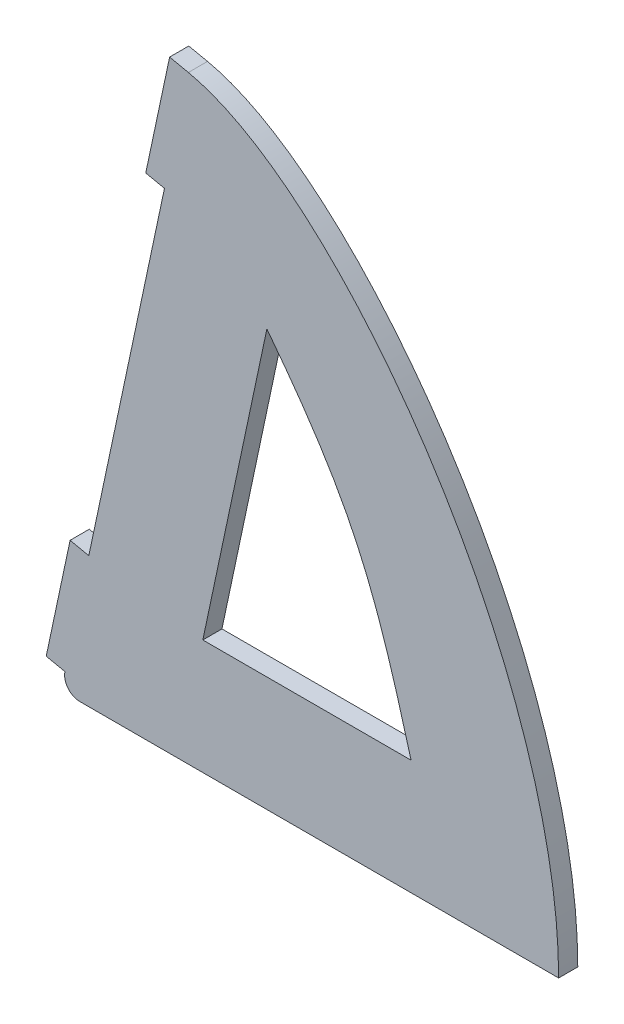
SolidWorks part; units mm, degrees
ref_plane "Front Plane" through (0, 0, 0) normal (0, 0, 1) x (1, 0, 0)
ref_plane "Top Plane" through (0, 0, 0) normal (0, 1, 0) x (1, 0, 0)
ref_plane "Right Plane" through (0, 0, 0) normal (1, 0, 0) x (0, 0, -1)
sketch "Sketch1" plane through (0, 0, 0) normal (0, 0, 1) x (1, 0, 0)
  line L0 (17.1631, 80.7461) -> (4.6129, 21.7018)
  line L1 (3.1366, 0) -> (82.55, 0)
  line L2 (-133.6738, 132.2831) -> (-145.319, 134.7583) construction
  line L3 (21.1238, 99.3798) -> (44.8991, 94.3262) construction
  line L4 (-1.4509, 104.1782) -> (-8.3265, 105.6397) construction
  line L5 (82.55, -41.9989) -> (82.55, 41.9989) construction
  line L6 (21.1238, 99.3798) -> (18.0182, 100.0399)
  line L7 (18.0182, 100.0399) -> (14.0575, 81.4062)
  line L8 (14.0575, 81.4062) -> (17.1631, 80.7461)
  line L9 (0.6521, 3.0681) -> (-2.4535, 3.7282)
  line L10 (-2.4535, 3.7282) -> (1.5072, 22.3619)
  line L11 (34.1512, 69.0431) -> (23.5248, 19.05)
  line L12 (23.5248, 19.05) -> (58.0733, 19.05)
  line L13 (1.5072, 22.3619) -> (4.6129, 21.7018)
  line L14 (0.6521, 3.0681) -> (4.6129, 21.7018) construction
  line L15 (17.1631, 80.7461) -> (21.1238, 99.3798) construction
  arc A0 (0.6521, 3.0681) -> (3.1366, 0) centre (3.1366, 2.54) ccw
  spline S0 degree 3 poles (21.1238, 99.3798) (46.7067, 93.942) (82.55, 42.6423) (82.55, 0) knots 0 0 0 0 1 1 1 1
  spline S1 degree 3 poles (34.1512, 69.0431) (48.6666, 50.286) (52.0895, 40.772) (58.0733, 19.05) knots 0 0 0 0 1 1 1 1
  point P8 (0, 0)
  point P23 (0, 0)
  dimension "D5" = 2.54
  dimension "D1" = 78
  dimension "D2" = 82.55
  dimension "D3" = 101.6
  dimension "D4" = 19.05
  dimension "D6" = 19.05
  dimension "D7" = 3.175
  dimension "D8" = 19.05
  dimension "D9" = 19.05
  dimension "D10" = 3.175
extrude "Boss-Extrude1" add sketch "Sketch1" along normal blind 3.175
